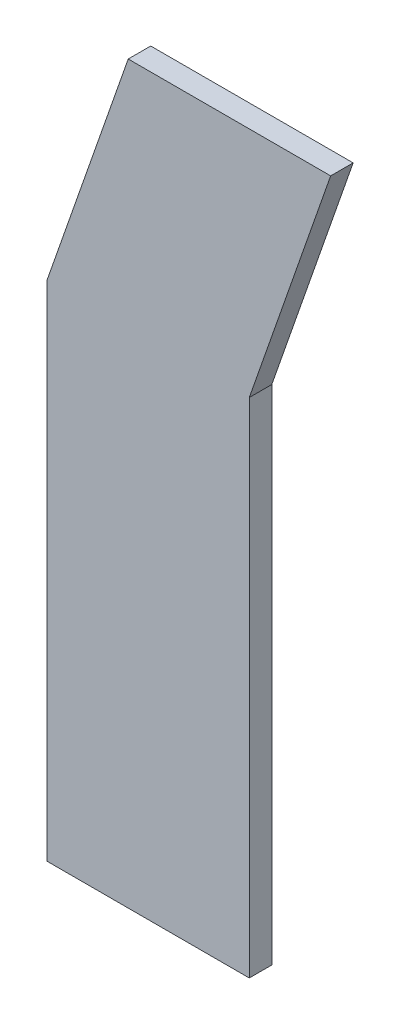
SolidWorks part; units mm, degrees
ref_plane "Front" through (0, 0, 0) normal (0, 0, 1) x (1, 0, 0)
ref_plane "Top" through (0, 0, 0) normal (0, 1, 0) x (1, 0, 0)
ref_plane "Right" through (0, 0, 0) normal (1, 0, 0) x (0, 0, -1)
sketch "Sketch1" plane through (0, 0, 0) normal (0, 0, 1) x (1, 0, 0)
  line L0 (0, 0) -> (72.3643, 206.8715)
  line L2 (0, 0) -> (0, -447)
  line L3 (0, -447) -> (180, -447)
  line L4 (180, -447) -> (180, 0)
  line L5 (180, 0) -> (252.3643, 206.8715)
  line L8 (252.3643, 206.8715) -> (72.3643, 206.8715)
  point P9 (238.0504, 206.8715)
  point P10 (323.3634, 206.8715)
  dimension "D1" = 180
  dimension "D2" = 160.72
  dimension "D3" = 447
  dimension "D4" = 219.163
  dimension "D5" = 180
extrude "Boss-Extrude1" add sketch "Sketch1" along normal blind 20
